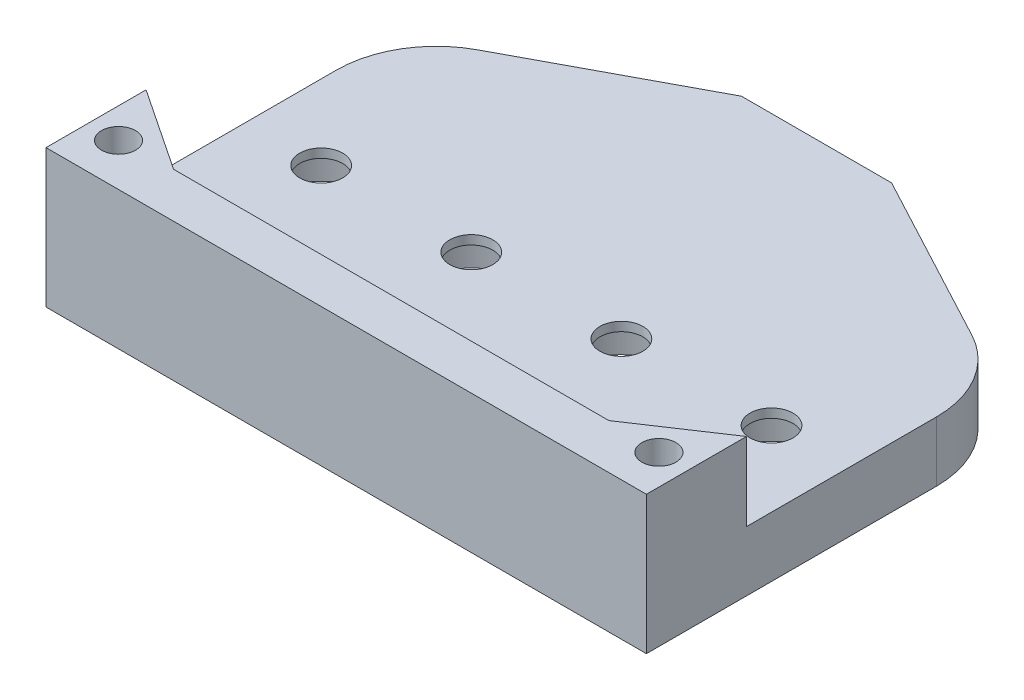
SolidWorks part; units mm, degrees
ref_plane "Front Plane" through (0, 0, 0) normal (0, 0, 1) x (1, 0, 0)
ref_plane "Top Plane" through (0, 0, 0) normal (0, 1, 0) x (1, 0, 0)
ref_plane "Right Plane" through (0, 0, 0) normal (1, 0, 0) x (0, 0, -1)
sketch "Sketch2" plane through (0, 0, 0) normal (0, 1, 0) x (1, 0, 0)
  line L0 (0, 0) -> (0, 35)
  line L1 (0, 35) -> (22.5, 47)
  line L2 (22.5, 47) -> (37.5, 47)
  line L3 (37.5, 47) -> (60, 35)
  line L4 (60, 35) -> (60, 0)
  line L5 (60, 0) -> (0, 0)
  line L6 (22.5, 20) -> (37.5, 20) construction
  line L7 (30, 47) -> (30, 0) construction
  circle A0 centre (7.5, 20) radius 2.15
  circle A1 centre (22.5, 20) radius 2.15
  circle A2 centre (37.5, 20) radius 2.15
  circle A3 centre (52.5, 20) radius 2.15
  point P17 (30, 20)
  dimension "D5" = 4.3
  dimension "D7" = 15
  dimension "D8" = 15
  dimension "D9" = 15
  dimension "D6" = 20
  dimension "D1" = 60
  dimension "D2" = 35
  dimension "D3" = 15
  dimension "D4" = 12
extrude "Boss-Extrude1" add sketch "Sketch2" along normal blind 6
sketch "Sketch3" plane through (0, 6, 0) normal (0, 1, 0) x (1, 0, 0)
  line L0 (0, 0) -> (0, 10)
  line L1 (0, 35) -> (0, 0) construction
  line L2 (0, 10) -> (15, 0)
  line L3 (0, 0) -> (60, 0) construction
  line L4 (15, 0) -> (0, 0)
  line L5 (60, 0) -> (60, 10)
  line L6 (60, 0) -> (60, 35) construction
  line L7 (60, 10) -> (45, 0)
  line L8 (45, 0) -> (60, 0)
  line L9 (51.75, 4.5) -> (8.25, 4.5)
  line M8 (0, 0) -> (60, 0)
  line M9 (60, 0) -> (60, 35)
  line M13 (0, 35) -> (0, 0)
  dimension "D1" = 15
  dimension "D2" = 10
  dimension "D3" = 4.5
extrude "Boss-Extrude2" add sketch "Sketch3" along normal blind 7.8 contours L2 M13 M8 | L7 L9 L2 M8 | L7 M9 M8 region at (5, 6, -3.3333) region at (30, 6, -2.3878) region at (55, 6, -3.3333)
sketch "Sketch4" plane through (0, 13.8, 0) normal (0, 1, 0) x (1, 0, 0)
  line L0 (0, 0) -> (60, 0) construction
  line L1 (0, 10) -> (0, 0) construction
  line L2 (60, 0) -> (60, 10) construction
  circle A0 centre (3, 4.25) radius 1.7
  circle A1 centre (57, 4.25) radius 1.7
  dimension "D1" = 3.4
  dimension "D2" = 4.25
  dimension "D3" = 3
  dimension "D4" = 3
extrude "Cut-Extrude1" cut sketch "Sketch4" against normal through all
sketch "Sketch5" plane through (0, 0, 0) normal (0, 1, 0) x (1, 0, 0)
  circle A0 centre (7.5, 20) radius 6.55
  circle A1 centre (22.5, 20) radius 6.55
  circle A2 centre (37.5, 20) radius 6.55
  circle A3 centre (52.5, 20) radius 6.55
  dimension "D1" = 13.1
extrude "Cut-Extrude2" cut sketch "Sketch5" along normal blind 5.1
fillet "Fillet1" radius 10 2 edges at (0, 3, -35) (60, 3, -35)
sketch "Sketch6" plane through (0, 0, 0) normal (0, -1, 0) x (-1, 0, 0)
  line L0 (-25, 42.25) -> (-35, 42.25) construction
  line L1 (-37.5, 47) -> (-22.5, 47) construction
  line L2 (-3, 4.25) -> (-25, 4.25) construction
  circle A0 centre (-25, 42.25) radius 2.6
  circle A1 centre (-35, 42.25) radius 2.6
  circle A2 centre (-35, 4.25) radius 2.6
  circle A3 centre (-25, 4.25) radius 2.6
  point P10 (-30, 47)
  point P11 (-30, 42.25)
  dimension "D1" = 5.2
  dimension "D2" = 10
  dimension "D3" = 38
extrude "Cut-Extrude3" cut sketch "Sketch6" against normal blind 5
